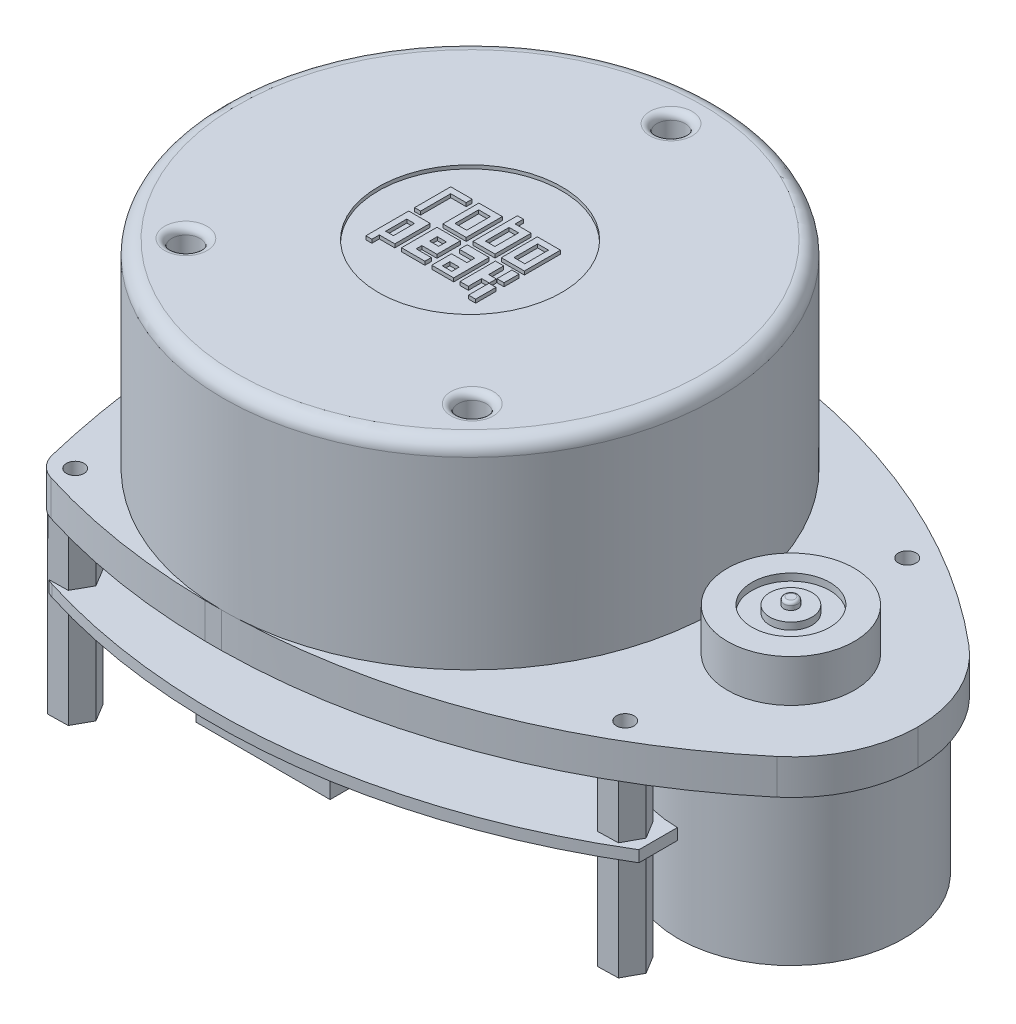
SolidWorks part; units mm, degrees
ref_plane "Спереди" through (0, 0, 0) normal (0, 0, 1) x (1, 0, 0)
ref_plane "Сверху" through (0, 0, 0) normal (0, 1, 0) x (1, 0, 0)
ref_plane "Справа" through (0, 0, 0) normal (1, 0, 0) x (0, 0, -1)
sketch "Эскиз1" plane through (0, 0, 0) normal (0, 1, 0) x (1, 0, 0)
  line L1 (-49.25, 35) -> (49.25, 35)
  line L2 (-49.25, 35) -> (-49.25, -35)
  line L3 (-49.25, -35) -> (49.25, -35)
  line L4 (49.25, 35) -> (49.25, -35)
  line L5 (-49.25, 35) -> (49.25, -35) construction
  line L6 (-49.25, -35) -> (49.25, 35) construction
  point P0 (0, 0)
  dimension "D1" = 98.5
  dimension "D2" = 70
extrude "Бобышка-Вытянуть1" add sketch "Эскиз1" along normal blind 5
sketch "Эскиз2" plane through (0, 5, 0) normal (0, 1, 0) x (1, 0, 0)
  line L0 (-49.25, 35) -> (-49.25, -35) construction
  circle A0 centre (-14.25, 0) radius 35
  point P2 (-49.25, 0)
  point P3 (-49.25, 0)
extrude "Бобышка-Вытянуть2" add sketch "Эскиз2" along normal blind 28.1
sketch "Эскиз3" plane through (0, 33.1, 0) normal (0, 1, 0) x (1, 0, 0)
  line L0 (-14.25, 0) -> (-14.25, 50000) construction
  line L1 (-14.25, -20) -> (-26.2883, -20) construction
  line L2 (-49.25, -35) -> (-14.25, -35) construction
  circle A0 centre (-14.25, 28.5) radius 2
  circle A1 centre (-34.5539, -20) radius 2
  circle A2 centre (6.0539, -20) radius 2
  arc A3 (-49.25, 0) -> (-14.25, -35) centre (-14.25, 0) ccw construction
  circle A4 centre (-14.25, 0) radius 35 construction
  dimension "D2" = 4
  dimension "D1" = 6.5
  dimension "D3" = 15
  dimension "D4" = 28.5
  dimension "D5" = 28.5
extrude "Вырез-Вытянуть1" cut sketch "Эскиз3" against normal blind 5
fillet "Скругление1" radius 2 1 edges at (-14.25, 33.1, 35)
fillet "Скругление2" radius 1 3 edges at (6.0539, 33.1, 22) (-34.5539, 33.1, 22) (-14.25, 33.1, -26.5)
sketch "Эскиз4" plane through (0, 33.1, 0) normal (0, 1, 0) x (1, 0, 0)
  line L0 (-22.1152, -6.9149) -> (-22.1152, -0.8316)
  line L1 (-22.1152, -0.8316) -> (-19.0735, -0.8316)
  line L2 (-19.0735, -0.8316) -> (-19.0735, -5.8538)
  line L3 (-19.0735, -5.8538) -> (-21.2663, -5.8538)
  line L4 (-21.2663, -5.8538) -> (-21.2663, -6.9149)
  line L5 (-21.2663, -6.9149) -> (-22.1152, -6.9149)
  line L6 (-22.1152, 0) -> (-22.1152, 5.1201)
  line L7 (-22.1152, 5.1201) -> (-19.0735, 5.1201)
  line L8 (-19.0735, 5.1201) -> (-19.0735, 4.2707)
  line L9 (-19.0735, 4.2707) -> (-21.2663, 4.2707)
  line L10 (-21.2663, 4.2707) -> (-21.2663, 0)
  line L11 (-21.2663, 0) -> (-22.1152, 0)
  line L12 (-21.2663, -1.9579) -> (-20.1699, -1.9579)
  line L13 (-20.1699, -1.9579) -> (-20.1699, -4.9509)
  line L14 (-20.1699, -4.9509) -> (-21.2663, -4.9509)
  line L15 (-21.2663, -4.9509) -> (-21.2663, -1.9579)
  line L16 (-13.8296, 0) -> (-13.8296, 6.293)
  line L17 (-18.1168, 0) -> (-14.8003, 0)
  line L18 (-18.1168, 0) -> (-18.1168, 5.1201)
  line L19 (-18.1168, 5.1201) -> (-14.8003, 5.1201)
  line L20 (-14.8003, 0) -> (-14.8003, 5.1201)
  line L21 (-9.8255, 5.1201) -> (-6.5494, 5.1201)
  line L22 (-9.8255, 5.1201) -> (-9.8255, 0)
  line L23 (-9.8255, 0) -> (-6.5494, 0)
  line L24 (-6.5494, 5.1201) -> (-6.5494, 0)
  line L25 (-8.9357, 4.2707) -> (-7.3988, 4.2707)
  line L26 (-8.9357, 4.2707) -> (-8.9357, 0.9137)
  line L27 (-8.9357, 0.9137) -> (-7.3988, 0.9137)
  line L28 (-7.3988, 4.2707) -> (-7.3988, 0.9137)
  line L29 (-17.3079, 4.2707) -> (-15.6497, 4.2707)
  line L30 (-17.3079, 4.2707) -> (-17.3079, 0.9137)
  line L31 (-17.3079, 0.9137) -> (-15.6497, 0.9137)
  line L32 (-15.6497, 4.2707) -> (-15.6497, 0.9137)
  line L33 (-12.9802, 4.2707) -> (-11.6455, 4.2707)
  line L34 (-12.9802, 4.2707) -> (-12.9802, 0.9137)
  line L35 (-12.9802, 0.9137) -> (-11.6455, 0.9137)
  line L36 (-11.6455, 4.2707) -> (-11.6455, 0.9137)
  line L37 (-12.9802, -4.142) -> (-11.6455, -4.142)
  line L38 (-12.9802, -4.142) -> (-12.9802, -5.1936)
  line L39 (-12.9802, -5.1936) -> (-11.6455, -5.1936)
  line L40 (-11.6455, -4.142) -> (-11.6455, -5.1936)
  line L41 (-16.9439, -1.9579) -> (-15.6497, -1.9579)
  line L42 (-16.9439, -1.9579) -> (-16.9439, -3.0499)
  line L43 (-16.9439, -3.0499) -> (-15.6497, -3.0499)
  line L44 (-15.6497, -1.9579) -> (-15.6497, -3.0499)
  line L46 (-7.5508, -0.7643) -> (-6.5494, -0.7643)
  line L47 (-7.5508, -0.7643) -> (-7.5508, -2.8858)
  line L48 (-7.5508, -2.8858) -> (-6.5494, -2.8858)
  line L49 (-6.5494, -0.7643) -> (-6.5494, -2.8858)
  line L50 (-6.5494, -6.9149) -> (-7.5508, -6.9149)
  line L51 (-6.5494, -6.9149) -> (-6.5494, -4.0216)
  line L52 (-6.5494, -4.0216) -> (-7.5508, -4.0216)
  line L53 (-13.8296, 6.293) -> (-12.9802, 6.293)
  line L54 (-12.9802, 6.293) -> (-12.9802, 5.1201)
  line L55 (-12.9802, 5.1201) -> (-10.7153, 5.1201)
  line L56 (-10.7153, 5.1201) -> (-10.7153, 0)
  line L57 (-10.7153, 0) -> (-13.8296, 0)
  line L58 (-9.8255, -0.8316) -> (-8.6437, -0.8316)
  line L59 (-8.6437, -0.8316) -> (-8.6437, -2.9608)
  line L60 (-8.6437, -2.9608) -> (-7.5508, -2.9608)
  line L61 (-9.8255, -0.8316) -> (-9.8255, -5.8538)
  line L62 (-9.8255, -5.8538) -> (-8.6437, -5.8538)
  line L63 (-8.6437, -5.8538) -> (-8.6437, -3.9573)
  line L64 (-8.6437, -3.9573) -> (-7.5508, -3.9573)
  line L65 (-7.5508, -2.9608) -> (-7.5508, -3.9573)
  line L66 (-13.8296, -0.8316) -> (-10.7153, -0.8316)
  line L67 (-10.7153, -0.8316) -> (-10.7153, -5.8538)
  line L68 (-10.7153, -5.8538) -> (-13.8296, -5.8538)
  line L69 (-13.8296, -5.8538) -> (-13.8296, -3.0499)
  line L70 (-13.8296, -3.0499) -> (-11.6455, -3.0499)
  line L71 (-11.6455, -3.0499) -> (-11.6455, -1.9408)
  line L72 (-11.6455, -1.9408) -> (-13.8296, -1.9408)
  line L73 (-13.8296, -1.9408) -> (-13.8296, -0.8316)
  line L74 (-18.1168, -0.8316) -> (-14.8003, -0.8316)
  line L75 (-14.8003, -0.8316) -> (-14.8003, -4.142)
  line L76 (-14.8003, -4.142) -> (-16.9439, -4.142)
  line L77 (-16.9439, -4.142) -> (-16.9439, -4.9509)
  line L78 (-16.9439, -4.9509) -> (-14.8003, -4.9509)
  line L79 (-14.8003, -4.9509) -> (-14.8003, -5.8538)
  line L80 (-14.8003, -5.8538) -> (-18.1168, -5.8538)
  line L81 (-18.1168, -5.8538) -> (-18.1168, -0.8316)
  line L82 (-7.5508, -6.9149) -> (-7.5508, -4.0216)
  circle A0 centre (-14.25, 0) radius 13
  dimension "D1" = 26
extrude "Вырез-Вытянуть3" cut sketch "Эскиз4" against normal blind 0.5 contours A0 L50 L82 L52 L51 L72 L73 L66 L67 L68 L69 L70 L71 L56 L57 L16 L53 L54 L55 L10 L11 L6 L7 L8 L9 L4 L5 L0 L1 L2 L3 L20 L17 L18 L19 L21 L24 L23 L22 L46 L49 L48 L47 | L32 L29 L30 L31 | L36 L33 L34 L35 | L28 L25 L26 L27 | L44 L41 L42 L43 | L15 L14 L13 L12 | L37 L40 L39 L38 region at (-20.7181, 33.1, 3.4544) region at (-8.1672, 33.1, -2.5922) region at (-16.4788, 33.1, -2.5922) region at (-12.3129, 33.1, -2.5922) region at (-16.2968, 33.1, 2.5039) region at (-14.2871, 33.1, -0.0991)
sketch "Эскиз5" plane through (0, 5, 0) normal (0, 1, 0) x (1, 0, 0)
  line L0 (-42.25, 30.7255) -> (-42.25, -39.5827) construction
  line L1 (27.75, 26.9972) -> (27.75, -49973.0028) construction
  line L2 (-49.25, 0) -> (49950.75, 0) construction
  circle A0 centre (-14.25, 0) radius 33 construction
  circle A1 centre (-42.25, 28) radius 1.25
  circle A2 centre (27.75, 20) radius 1.25
  circle A3 centre (27.75, -20) radius 1.25
  circle A4 centre (-42.25, -28) radius 1.25
  point P4 (-14.25, 33)
  dimension "D1" = 28
  dimension "D3" = 2.5
  dimension "D2" = 42
  dimension "D4" = 28
  dimension "D5" = 20
extrude "Вырез-Вытянуть4" cut sketch "Эскиз5" against normal blind 5
sketch "Эскиз6" plane through (0, 5, 0) normal (0, 1, 0) x (1, 0, 0)
  line L0 (49.25, 0) -> (50049.25, 0) construction
  line L1 (49.25, -35) -> (49.25, 35) construction
  circle A0 centre (31.25, 0) radius 9
  arc A1 (-14.25, -35) -> (-14.25, 35) centre (-14.25, 0) ccw construction
  point P4 (49.25, 0)
  dimension "D1" = 18
  dimension "D2" = 45.5
extrude "Бобышка-Вытянуть3" add sketch "Эскиз6" along normal blind 7
sketch "Эскиз7" plane through (0, 12, 0) normal (0, 1, 0) x (1, 0, 0)
  circle A0 centre (31.25, 0) radius 9
  circle A1 centre (31.25, 0) radius 0.9935
extrude "Вырез-Вытянуть5" cut sketch "Эскиз7" against normal blind 1
sketch "Эскиз8" plane through (0, 11, 0) normal (0, 1, 0) x (1, 0, 0)
  circle A0 centre (31.25, 0) radius 3.0011
  circle A1 centre (31.25, 0) radius 5.5217
extrude "Вырез-Вытянуть6" cut sketch "Эскиз8" against normal blind 1
fillet "Скругление3" radius 0.4 1 edges at (31.25, 12, 0.9935)
sketch "Эскиз9" plane through (0, 5, 0) normal (0, 1, 0) x (1, 0, 0)
  circle A0 centre (31.25, 0) radius 16
  dimension "D1" = 32
extrude "Бобышка-Вытянуть4" add sketch "Эскиз9" against normal blind 27
sketch "Эскиз10" plane through (0, 0, 0) normal (0, -1, 0) x (1, 0, 0)
  line L0 (-49.25, 0) -> (49950.75, 0) construction
  line L1 (-40.8546, 25.4729) -> (-39.3638, 27.9449)
  line L2 (-39.3638, 27.9449) -> (-40.7592, 30.472)
  line L3 (-40.7592, 30.472) -> (-43.6454, 30.5271)
  line L4 (-43.6454, 30.5271) -> (-45.1362, 28.0551)
  line L5 (-45.1362, 28.0551) -> (-43.7408, 25.528)
  line L6 (-43.7408, 25.528) -> (-40.8546, 25.4729)
  line L7 (29.2571, 22.4621) -> (26.3713, 22.5363)
  line L8 (26.3713, 22.5363) -> (24.8642, 20.0742)
  line L9 (24.8642, 20.0742) -> (26.2429, 17.5379)
  line L10 (26.2429, 17.5379) -> (29.1287, 17.4637)
  line L11 (29.1287, 17.4637) -> (30.6358, 19.9258)
  line L12 (30.6358, 19.9258) -> (29.2571, 22.4621)
  line L13 (30.6358, -19.9258) -> (29.2571, -22.4621)
  line L14 (29.1287, -17.4637) -> (30.6358, -19.9258)
  line L15 (26.2429, -17.5379) -> (29.1287, -17.4637)
  line L16 (24.8642, -20.0742) -> (26.2429, -17.5379)
  line L17 (26.3713, -22.5363) -> (24.8642, -20.0742)
  line L18 (29.2571, -22.4621) -> (26.3713, -22.5363)
  line L19 (-43.7408, -25.528) -> (-40.8546, -25.4729)
  line L20 (-45.1362, -28.0551) -> (-43.7408, -25.528)
  line L21 (-43.6454, -30.5271) -> (-45.1362, -28.0551)
  line L22 (-40.7592, -30.472) -> (-43.6454, -30.5271)
  line L23 (-39.3638, -27.9449) -> (-40.7592, -30.472)
  line L24 (-40.8546, -25.4729) -> (-39.3638, -27.9449)
  circle A0 centre (-42.25, 28) radius 2.5 construction
  circle A1 centre (27.75, 20) radius 2.5 construction
  circle A2 centre (27.75, -20) radius 2.5 construction
  circle A3 centre (-42.25, -28) radius 2.5 construction
  point P17 (27.75, 20)
  dimension "D1" = 5
  dimension "D2" = 5
extrude "Бобышка-Вытянуть5" add sketch "Эскиз10" along normal blind 24.6
sketch "Эскиз11" plane through (0, 5, 0) normal (0, 1, 0) x (1, 0, 0)
  circle A0 centre (-14.25, 0) radius 26
  dimension "D1" = 52
extrude "Бобышка-Вытянуть6" add sketch "Эскиз11" against normal blind 8
fillet "Скругление4" radius 1 1 edges at (-14.25, -3, 26)
sketch "Эскиз12" plane through (0, 5, 0) normal (0, 1, 0) x (1, 0, 0)
  line L1 (49.25, -35) -> (49.25, 35) construction
  line L2 (-49.25, 0) -> (-50049.25, 0) construction
  line L4 (-54.0511, 37.7308) -> (52.2004, 37.7308)
  line L5 (-54.0511, 37.7308) -> (-54.0511, -37.8351)
  line L6 (-54.0511, -37.8351) -> (52.2004, -37.8351)
  line L7 (52.2004, 37.7308) -> (52.2004, -37.8351)
  arc A0 (-49.25, 0) -> (-45.5286, 27.9743) centre (86.6751, -3.8473) cw
  circle A1 centre (-14.25, 0) radius 35 construction
  arc A3 (49.25, 0) -> (42.909, 13.5993) centre (31.4018, -0.0442) ccw
  arc A4 (-49.25, 0) -> (-14.25, -35) centre (-14.25, 0) ccw construction
  arc A5 (-42.835, 30.8555) -> (42.909, 13.5993) centre (-15.6796, -55.8665) cw
  arc A6 (-45.5286, 27.9743) -> (-42.835, 30.8555) centre (-41.6397, 27.0383) cw
  arc A7 (-45.5286, -27.9743) -> (-42.835, -30.8555) centre (-41.6397, -27.0383) ccw
  arc A8 (-42.835, -30.8555) -> (42.909, -13.5993) centre (-15.6796, 55.8665) ccw
  arc A9 (49.25, 0) -> (42.909, -13.5993) centre (31.4018, 0.0442) cw
  arc A10 (-49.25, 0) -> (-45.5286, -27.9743) centre (86.6751, 3.8473) ccw
  dimension "D1" = 4
extrude "Вырез-Вытянуть7" cut sketch "Эскиз12" against normal blind 8
fillet "Скругление5" radius 100 1 edges at (-49.25, 2.5, 0)
sketch "Эскиз13" plane through (0, 0, 0) normal (0, -1, 0) x (1, 0, 0)
  line L0 (31.5536, 21.8603) -> (31.5536, 16.4)
  line L1 (31.5536, -16.4) -> (31.5536, -21.8603)
  arc A0 (-49.0982, 0) -> (-45.3768, 27.9743) centre (86.8269, -3.8473) cw
  arc A1 (31.5536, 16.4) -> (31.5536, -16.4) centre (31.5536, 0) ccw
  arc A2 (-42.6831, 30.8555) -> (31.5536, 21.8603) centre (-15.5278, -55.8665) cw
  arc A3 (-45.3768, 27.9743) -> (-42.6831, 30.8555) centre (-41.4878, 27.0383) cw
  arc A4 (-45.3768, -27.9743) -> (-42.6831, -30.8555) centre (-41.4878, -27.0383) ccw
  arc A5 (-42.6831, -30.8555) -> (31.5536, -21.8603) centre (-15.5278, 55.8665) ccw
  arc A7 (-49.0982, 0) -> (-45.3768, -27.9743) centre (86.8269, 3.8473) ccw
  arc A8 (-48.5248, 10.6929) -> (-48.5248, -10.6929) centre (50.9018, 0) ccw construction
  point P16 (-49.0982, 0)
  point P21 (-49.0982, 0)
  dimension "D1" = 4
  dimension "D2" = 32.8
extrude "Бобышка-Вытянуть7" add sketch "Эскиз13" along normal blind 1.6 from offset 8
sketch "Эскиз14" plane through (0, -9.6, 0) normal (0, -1, 0) x (1, 0, 0)
  line L1 (-24.0982, 30) -> (-4.0982, 30)
  line L2 (-24.0982, 30) -> (-24.0982, 25)
  line L3 (-24.0982, 25) -> (-4.0982, 25)
  line L4 (-4.0982, 30) -> (-4.0982, 25)
  circle A0 centre (-14.25, 0) radius 35 construction
  point P4 (-14.0982, 30)
  dimension "D1" = 5
  dimension "D2" = 20
  dimension "D3" = 35
  dimension "D4" = 30
extrude "Бобышка-Вытянуть8" add sketch "Эскиз14" along normal blind 6
chamfer "Фаска1" distance 1 angle 45 1 edges at (-24.0982, -12.6, 30)
